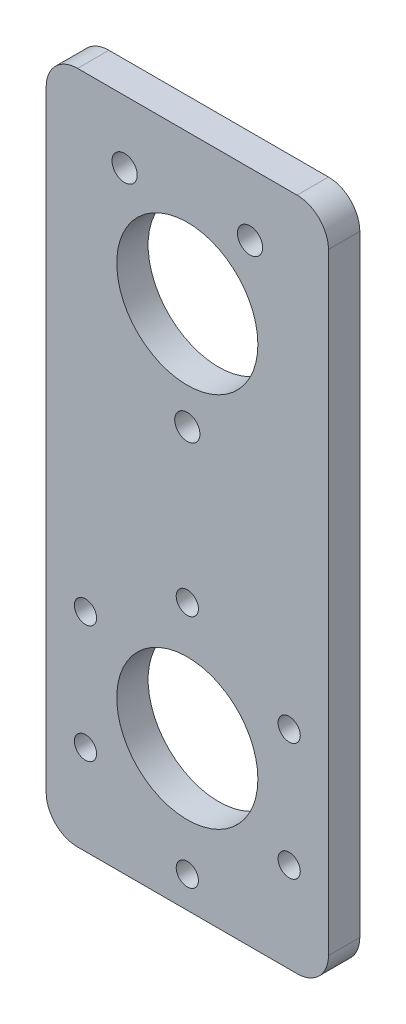
SolidWorks part; units mm, degrees
ref_plane "Front Plane" through (0, 0, 0) normal (0, 0, 1) x (1, 0, 0)
ref_plane "Top Plane" through (0, 0, 0) normal (0, 1, 0) x (1, 0, 0)
ref_plane "Right Plane" through (0, 0, 0) normal (1, 0, 0) x (0, 0, -1)
sketch "Sketch1" plane through (0, 0, 0) normal (0, 0, 1) x (1, 0, 0)
  line L0 (0, -38.1) -> (0, 38.1) construction
  line L2 (-28.575, 68.2625) -> (28.575, 68.2625)
  line L3 (-28.575, 68.2625) -> (-28.575, -68.2625)
  line L4 (-28.575, -68.2625) -> (28.575, -68.2625)
  line L5 (28.575, 68.2625) -> (28.575, -68.2625)
  line L6 (-28.575, 68.2625) -> (28.575, -68.2625) construction
  line L7 (-28.575, -68.2625) -> (28.575, 68.2625) construction
  circle A0 centre (0, 38.1) radius 14.2875
  circle A1 centre (0, -38.1) radius 14.2875
  point P7 (0, 0)
  point P18 (0, -38.1)
  dimension "D1" = 28.575
  dimension "D2" = 76.2
  dimension "D6" = 136.525
  dimension "D7" = 57.15
extrude "Boss-Extrude1" add sketch "Sketch1" along normal mid plane 6.35
fillet "Fillet1" radius 6.35 4 edges at (28.575, -68.2625, 0) (-28.575, -68.2625, 0) (-28.575, 68.2625, 0) (28.575, 68.2625, 0)
hole_wizard "#8 Clearance Hole1" positions "Sketch3" profile "Sketch2" hole size "#8" standard "ANSI Inch" end condition through all
sketch "Sketch3" plane through (0, 0, 3.175) normal (0, 0, 1) x (1, 0, 0)
  circle A0 centre (0, -38.1) radius 14.2875 construction
  point P0 (0, -14.2875)
  point P10 (20.6222, -26.1937)
  point P11 (20.6222, -50.0062)
  point P12 (0, -61.9125)
  point P13 (-20.6222, -50.0063)
  point P14 (-20.6222, -26.1938)
  point P15 (0, -38.1)
  dimension "D1" = 23.8125
  dimension "D2" = 6
sketch "Sketch2" plane through (0, -14.2875, 3.175) normal (1, 0, 0) x (0, -1, 0)
  line L0 (0, 0) -> (0, 6.35)
  line L1 (0, 6.35) -> (2.2479, 6.35)
  line L2 (2.2479, 6.35) -> (2.2479, 0)
  line L5 (2.2479, 0) -> (0, 0)
  line L11 (0, -6.35) -> (0, 107.95) construction
  dimension "Thru Hole Dia." = 4.4958
  dimension "Thru Hole Depth" = 6.35
hole_wizard "#10 Clearance Hole1" positions "Sketch7" profile "Sketch5" hole size "#10" standard "ANSI Inch" end condition through all
sketch "Sketch7" plane through (0, 0, 3.175) normal (0, 0, 1) x (1, 0, 0)
  line L0 (-12.7, 55.5625) -> (12.7, 55.5625) construction
  line L2 (22.225, 68.2625) -> (-22.225, 68.2625) construction
  circle A3 centre (0, 38.1) radius 15.875
  circle A4 centre (0, 38.1) radius 15.875 construction
  circle A5 centre (-12.7, 55.5625) radius 7.9375 construction
  circle A8 centre (0, 16.51) radius 7.9375 construction
  point P0 (-12.7, 55.5625)
  point P2 (12.7, 55.5625)
  point P9 (0, 55.5625)
  point P29 (0, 16.51)
  dimension "D4" = 15.875
  dimension "D1" = 25.4
  dimension "D2" = 12.7
  dimension "D5" = 21.59
  dimension "D3" = 1.5875
sketch "Sketch5" plane through (-12.7, 55.5625, 3.175) normal (1, 0, 0) x (0, -1, 0)
  line L0 (0, 0) -> (0, 6.35)
  line L1 (0, 6.35) -> (2.5527, 6.35)
  line L2 (2.5527, 6.35) -> (2.5527, 0)
  line L5 (2.5527, 0) -> (0, 0)
  line L11 (0, -6.35) -> (0, 107.95) construction
  dimension "Thru Hole Dia." = 5.1054
  dimension "Thru Hole Depth" = 6.35
